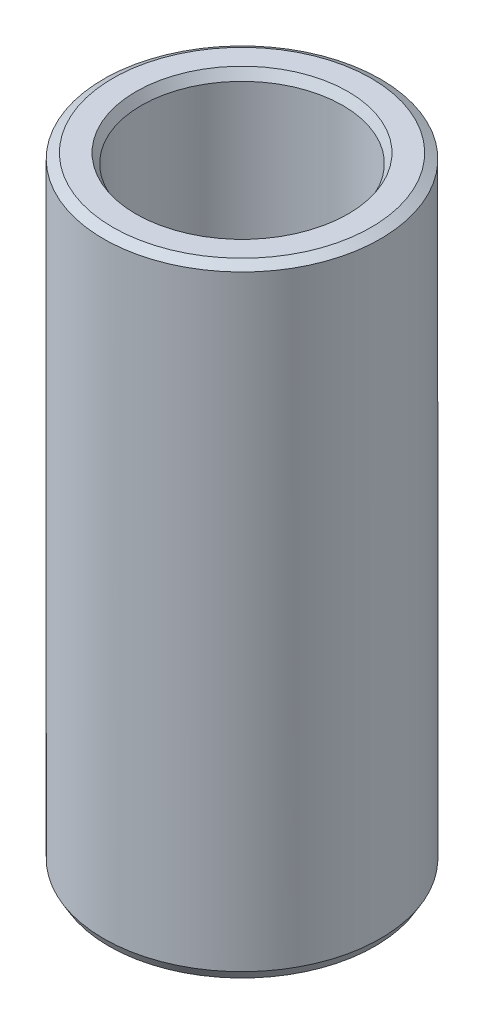
SolidWorks part; units mm, degrees
ref_plane "Front Plane" through (0, 0, 0) normal (0, 0, 1) x (1, 0, 0)
ref_plane "Top Plane" through (0, 0, 0) normal (0, 1, 0) x (1, 0, 0)
ref_plane "Right Plane" through (0, 0, 0) normal (1, 0, 0) x (0, 0, -1)
sketch "Sketch1" plane through (0, 0, 0) normal (0, 1, 0) x (1, 0, 0)
  circle A0 centre (0, 0) radius 25
  dimension "SLEEVE_OD" = 50
extrude "Boss-Extrude1" add sketch "Sketch1" along normal blind 112.0476
sketch "Sketch2" plane through (0, 0, 0) normal (0, 1, 0) x (1, 0, 0)
  circle A0 centre (0, 0) radius 18.1803
  dimension "BORE_D" = 36.3605
extrude "Cut-Extrude1" cut sketch "Sketch2" along normal through all
chamfer "Chamfer1" distance 0.9703 angle 60 4 edges at (0, 112.0476, 18.1803) (0, 0, 18.1803) (0, 0, 25) (0, 112.0476, 25) first distance on face at (0, 112.0476, 18.1803) first distance on face at (0, 0, 18.1803) first distance on face at (0, 112.0476, 25)
